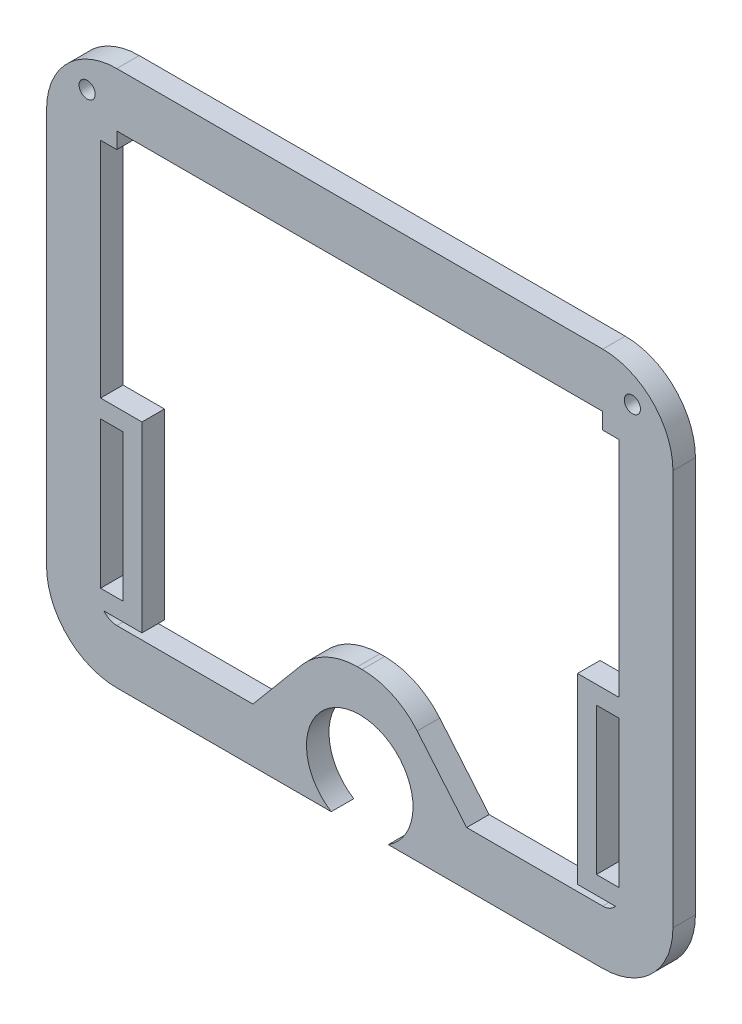
SolidWorks part; units mm, degrees
material "Delrin"
ref_plane "Front Plane" through (0, 0, 0) normal (0, 0, 1) x (1, 0, 0)
ref_plane "Top Plane" through (0, 0, 0) normal (0, 1, 0) x (1, 0, 0)
ref_plane "Right Plane" through (0, 0, 0) normal (1, 0, 0) x (0, 0, -1)
sketch "Sketch1" plane through (0, 0, 0) normal (0, 0, 1) x (1, 0, 0)
  line L0 (-17.145, -18.923) -> (-2.0127, -18.923)
  line L1 (-18.288, 13.97) -> (-18.288, -13.97)
  line L2 (-17.145, -15.113) -> (-7.5425, -15.113)
  line L3 (7.5425, -15.113) -> (17.145, -15.113)
  line L4 (18.288, 13.97) -> (18.288, -13.97)
  line L5 (26.2484, 21.5371) -> (-25.9352, -21.2801) construction
  line L6 (26.5681, -22.9118) -> (-24.5503, 21.1717) construction
  line L7 (2.0127, -18.923) -> (17.145, -18.923)
  line L8 (17.145, 15.113) -> (-17.145, 15.113)
  line L9 (-7.5425, -15.113) -> (-4.0566, -10.9586)
  line L10 (-22.098, 13.97) -> (-22.098, -13.97)
  line L11 (7.5425, -15.113) -> (4.0566, -10.9586)
  line L12 (-0.1651, -9.144) -> (0.1651, -9.144)
  line L13 (22.098, 13.97) -> (22.098, -13.97)
  line L14 (17.145, 18.923) -> (-17.145, 18.923)
  line L16 (-18.288, 13.97) -> (-17.145, 13.97)
  line L18 (0, 12.5532) -> (0, -24.2768) construction
  line L19 (17.145, 15.113) -> (17.145, 13.97)
  line L20 (-17.145, 13.97) -> (-17.145, 15.113)
  line L21 (17.145, 13.97) -> (18.288, 13.97)
  arc A0 (2.0127, -18.923) -> (-2.0127, -18.923) centre (0, -15.748) ccw
  arc A1 (-17.145, -15.113) -> (-18.288, -13.97) centre (-17.145, -13.97) cw
  arc A2 (-0.1651, -9.144) -> (-4.0566, -10.9586) centre (-0.1651, -14.224) ccw
  arc A3 (18.288, -13.97) -> (17.145, -15.113) centre (17.145, -13.97) cw
  arc A4 (17.145, 15.113) -> (18.288, 13.97) centre (17.145, 13.97) cw construction
  arc A5 (-17.145, -18.923) -> (-22.098, -13.97) centre (-17.145, -13.97) cw
  arc A6 (22.098, -13.97) -> (17.145, -18.923) centre (17.145, -13.97) cw
  arc A7 (17.145, 18.923) -> (22.098, 13.97) centre (17.145, 13.97) cw
  arc A8 (-17.145, 18.923) -> (-22.098, 13.97) centre (-17.145, 13.97) ccw
  circle A9 centre (-19.2352, 16.5881) radius 0.5715
  circle A10 centre (19.2352, 16.5881) radius 0.5715
  arc A11 (-17.145, 15.113) -> (-18.288, 13.97) centre (-17.145, 13.97) ccw construction
  arc A12 (0.1651, -9.144) -> (4.0566, -10.9586) centre (0.1651, -14.224) cw
  arc A18 (7.5425, -15.113) -> (-7.5425, -15.113) centre (0, -15.748) ccw construction
  point P0 (0, 0)
  dimension "D4" = 3.175
  dimension "D6" = 37.846
  dimension "D7" = 44.196
  dimension "D8" = 3.81
  dimension "D9" = 6.604
  dimension "D5" = 1.143
  dimension "D2" = 4.953
  dimension "D3" = 7.5184
  dimension "D10" = 5.08
  dimension "D11" = 5.08
  dimension "D1" = 50.8
  dimension "D12" = 25.4
extrude "Boss-Extrude1" add sketch "Sketch1" along normal blind 1.5875
sketch "Sketch2" plane through (-18.288, 0, 0) normal (1, 0, 0) x (0, 0, -1)
  line L0 (0, -3.0543) -> (-1.5875, -3.0543)
  line L1 (0, -13.4049) -> (-1.5875, -13.4049) construction
  line L2 (-1.5875, -15.113) -> (0, -15.113) construction
  line L3 (-1.5875, -15.113) -> (0, -15.113)
  line L4 (0, -13.97) -> (0, 13.97)
  line L5 (0, 13.97) -> (-1.5875, 13.97)
  line L6 (-1.5875, 13.97) -> (-1.5875, -13.97)
  line L7 (-1.5875, -13.97) -> (0, -13.97)
  line L8 (0, -13.97) -> (0, -1.7843)
  line L9 (-1.5875, -15.113) -> (-1.5875, -14.6749)
  line L10 (-1.5875, -1.7843) -> (-1.5875, -13.97)
  line L11 (-1.5875, -13.97) -> (0, -13.97)
  line L12 (0, -15.113) -> (0, -14.6749)
  line L13 (0, -1.7843) -> (-1.5875, -1.7843)
  line L15 (-1.5875, -1.7843) -> (-1.5875, -3.0543)
  line L16 (0, -3.0543) -> (0, -1.7843)
  line L17 (0, -7.9147) -> (0, -5.5961)
  line L18 (-1.5875, -7.9147) -> (-1.5875, -6.6447)
  line L19 (0, -13.4049) -> (-1.5875, -13.4049)
  line L21 (0, -14.6749) -> (-1.5875, -14.6749)
  line L22 (0, -14.6749) -> (0, -13.97)
  line L23 (-1.5875, -14.6749) -> (-1.5875, -13.97)
  line L24 (36.8526, -1.6809) -> (-36.7052, -4.4222) construction
  line L25 (31.7702, -4.4121) -> (-33.021, -6.8267) construction
  line L29 (36.8526, -14.7783) -> (-36.7052, -12.037) construction
  line M5 (0, -13.97) -> (0, 13.97)
  line M7 (-1.5875, 13.97) -> (-1.5875, -13.97)
  line M8 (-1.5875, -13.97) -> (0, -13.97)
  dimension "D1" = 0
  dimension "D2" = 1.27
  dimension "D4" = 1.27
extrude "Boss-Extrude2" add sketch "Sketch2" along normal blind 2.921 contours L13 L10 L0 M5 | L19 M5 M7 M8 | L23 L21 L22 M8 | L19 L8 L0 L10 M5 M7 region at (-18.288, -8.2296, 0.7937) region at (-18.288, -2.4193, 0.7937) region at (-18.288, -13.6874, 0.7937) region at (-18.288, -14.3224, 0.7937)
extrude "Cut-Extrude1" cut sketch "Sketch2<3>" along normal blind 1.5875 contours L19 L8 L10 region at (-18.288, -8.2296, 0.7937)
sketch "Sketch2<3>" plane through (-18.288, 0, 0) normal (1, 0, 0) x (0, 0, -1) same geometry as "Sketch2"
mirror "Mirror1" about plane through (0, 0, 0) normal (1, 0, 0) of "Cut-Extrude1", "Boss-Extrude2"
